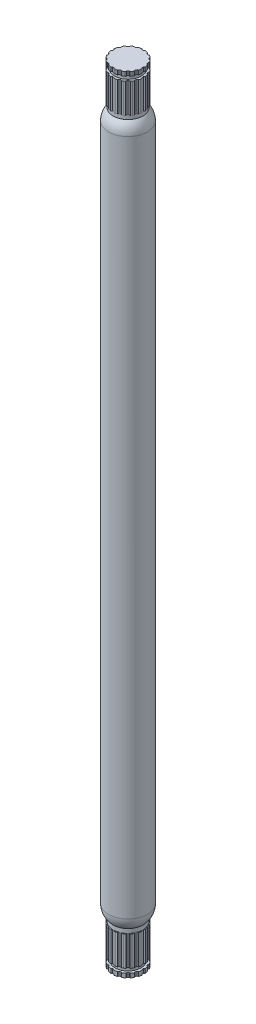
SolidWorks part; units mm, degrees
ref_plane "Front Plane" through (0, 0, 0) normal (0, 0, 1) x (1, 0, 0)
ref_plane "Top Plane" through (0, 0, 0) normal (0, 1, 0) x (1, 0, 0)
ref_plane "Right Plane" through (0, 0, 0) normal (1, 0, 0) x (0, 0, -1)
sketch "Sketch1" plane through (0, 0, 0) normal (0, 1, 0) x (1, 0, 0)
  circle A0 centre (0, 0) radius 11.65
  dimension "D1" = 23.3
extrude "Boss-Extrude1" add sketch "Sketch1" along normal blind 420
sketch "Sketch3" plane through (0, 420, 0) normal (0, 1, 0) x (1, 0, 0)
  circle A0 centre (0, 0) radius 8.9
  dimension "D1" = 17.8
extrude "Boss-Extrude2" add sketch "Sketch3" along normal blind 2.5
sketch "Sketch4" plane through (0, 422.5, 0) normal (0, 1, 0) x (1, 0, 0)
  line L0 (0, 12.8994) -> (0, 9.45) construction
  line L1 (-0.45, 8.8886) -> (0.45, 8.8886)
  line L2 (8.0398, -3.8173) -> (8.3842, -2.9858)
  line L3 (0.45, 8.8886) -> (0.9864, 9.3984)
  line L4 (-0.45, 8.8886) -> (-0.9864, 9.3984)
  line L5 (-0.9864, 9.3984) -> (-2.7571, 9.0388)
  line L6 (0.9864, 9.3984) -> (2.7571, 9.0388)
  line L7 (2.9858, 8.3842) -> (3.8173, 8.0398)
  line L8 (5.967, 6.6034) -> (6.6034, 5.967)
  line L9 (3.8173, 8.0398) -> (4.5079, 8.3055)
  line L10 (4.5079, 8.3055) -> (6.0063, 7.2957)
  line L11 (2.9858, 8.3842) -> (2.6853, 9.0605)
  line L12 (2.6853, 9.0605) -> (0.9118, 9.4059)
  line L15 (6.6034, 5.967) -> (7.3432, 5.9482)
  line L16 (7.3432, 5.9482) -> (8.341, 4.4419)
  line L17 (5.967, 6.6034) -> (5.9482, 7.3432)
  line L18 (5.9482, 7.3432) -> (4.4419, 8.341)
  line L19 (8.8886, -0.45) -> (8.8886, 0.45)
  line L20 (8.3842, 2.9858) -> (8.0398, 3.8173)
  line L21 (8.3842, 2.9858) -> (9.0605, 2.6853)
  line L22 (9.0605, 2.6853) -> (9.4059, 0.9118)
  line L23 (8.0398, 3.8173) -> (8.3055, 4.5079)
  line L24 (8.3055, 4.5079) -> (7.2957, 6.0063)
  line L27 (8.8886, -0.45) -> (9.3984, -0.9864)
  line L28 (9.3984, -0.9864) -> (9.0388, -2.7571)
  line L29 (8.8886, 0.45) -> (9.3984, 0.9864)
  line L30 (9.3984, 0.9864) -> (9.0388, 2.7571)
  line L33 (8.0398, -3.8173) -> (8.3055, -4.5079)
  line L34 (8.3055, -4.5079) -> (7.2957, -6.0063)
  line L35 (8.3842, -2.9858) -> (9.0605, -2.6853)
  line L36 (9.0605, -2.6853) -> (9.4059, -0.9118)
  line L37 (2.9858, -8.3842) -> (3.8173, -8.0398)
  line L38 (5.967, -6.6034) -> (6.6034, -5.967)
  line L39 (5.967, -6.6034) -> (5.9482, -7.3432)
  line L40 (5.9482, -7.3432) -> (4.4419, -8.341)
  line L41 (6.6034, -5.967) -> (7.3432, -5.9482)
  line L42 (7.3432, -5.9482) -> (8.341, -4.4419)
  line L45 (2.9858, -8.3842) -> (2.6853, -9.0605)
  line L46 (2.6853, -9.0605) -> (0.9118, -9.4059)
  line L47 (3.8173, -8.0398) -> (4.5079, -8.3055)
  line L48 (4.5079, -8.3055) -> (6.0063, -7.2957)
  line L49 (-2.9858, -8.3842) -> (-3.8173, -8.0398)
  line L50 (-0.45, -8.8886) -> (0.45, -8.8886)
  line L51 (-0.45, -8.8886) -> (-0.9864, -9.3984)
  line L52 (-0.9864, -9.3984) -> (-2.7571, -9.0388)
  line L53 (0.45, -8.8886) -> (0.9864, -9.3984)
  line L54 (0.9864, -9.3984) -> (2.7571, -9.0388)
  line L57 (-3.8173, -8.0398) -> (-4.5079, -8.3055)
  line L58 (-4.5079, -8.3055) -> (-6.0063, -7.2957)
  line L59 (-2.9858, -8.3842) -> (-2.6853, -9.0605)
  line L60 (-2.6853, -9.0605) -> (-0.9118, -9.4059)
  line L61 (-8.0398, -3.8173) -> (-8.3842, -2.9858)
  line L62 (-5.967, -6.6034) -> (-6.6034, -5.967)
  line L63 (-6.6034, -5.967) -> (-7.3432, -5.9482)
  line L64 (-7.3432, -5.9482) -> (-8.341, -4.4419)
  line L65 (-5.967, -6.6034) -> (-5.9482, -7.3432)
  line L66 (-5.9482, -7.3432) -> (-4.4419, -8.341)
  line L67 (0, -8.8886) -> (0, -8.9) construction
  line L68 (0, -9.45) -> (0, -14.34) construction
  line L69 (-8.3842, -2.9858) -> (-9.0605, -2.6853)
  line L70 (-9.0605, -2.6853) -> (-9.4059, -0.9118)
  line L71 (-8.0398, -3.8173) -> (-8.3055, -4.5079)
  line L72 (-8.3055, -4.5079) -> (-7.2957, -6.0063)
  line L73 (-8.8886, -0.45) -> (-8.8886, 0.45)
  line L75 (-8.8886, 0.45) -> (-9.3984, 0.9864)
  line L76 (-9.3984, 0.9864) -> (-9.0388, 2.7571)
  line L77 (-8.8886, -0.45) -> (-9.3984, -0.9864)
  line L78 (-9.3984, -0.9864) -> (-9.0388, -2.7571)
  line L79 (-8.3842, 2.9858) -> (-8.0398, 3.8173)
  line L81 (-8.0398, 3.8173) -> (-8.3055, 4.5079)
  line L82 (-8.3055, 4.5079) -> (-7.2957, 6.0063)
  line L83 (-8.3842, 2.9858) -> (-9.0605, 2.6853)
  line L84 (-9.0605, 2.6853) -> (-9.4059, 0.9118)
  line L85 (-3.8173, 8.0398) -> (-2.9858, 8.3842)
  line L86 (-6.6034, 5.967) -> (-5.967, 6.6034)
  line L87 (-5.967, 6.6034) -> (-5.9482, 7.3432)
  line L88 (-5.9482, 7.3432) -> (-4.4419, 8.341)
  line L89 (-6.6034, 5.967) -> (-7.3432, 5.9482)
  line L90 (-7.3432, 5.9482) -> (-8.341, 4.4419)
  line L93 (-2.9858, 8.3842) -> (-2.6853, 9.0605)
  line L94 (-2.6853, 9.0605) -> (-0.9118, 9.4059)
  line L95 (-3.8173, 8.0398) -> (-4.5079, 8.3055)
  line L96 (-4.5079, 8.3055) -> (-6.0063, 7.2957)
  circle A0 centre (0, 0) radius 9.45
  arc A1 (2.9858, 8.3842) -> (0.45, 8.8886) centre (0, 0) ccw
  arc A3 (8.3842, -2.9858) -> (8.8886, -0.45) centre (0, 0) ccw
  arc A4 (8.8886, 0.45) -> (8.3842, 2.9858) centre (0, 0) ccw
  arc A9 (-0.45, 8.8886) -> (-2.9858, 8.3842) centre (0, 0) ccw
  arc A10 (-3.8173, 8.0398) -> (-5.967, 6.6034) centre (0, 0) ccw
  arc A11 (-6.6034, 5.967) -> (-8.0398, 3.8173) centre (0, 0) ccw
  arc A12 (-8.3842, 2.9858) -> (-8.8886, 0.45) centre (0, 0) ccw
  arc A13 (-8.8886, -0.45) -> (-8.3842, -2.9858) centre (0, 0) ccw
  point P120 (0, 0)
  point P126 (0, 0)
  circle M1 centre (0, 0) radius 8.9
  dimension "D1" = 17.8
  dimension "D2" = 18.9
  dimension "D5" = 0.74
  dimension "D6" = 0.74
  dimension "D7" = 16
extrude "Boss-Extrude6" add sketch "Sketch4" along normal blind 17.8 contours L86 L79 L73 L61 L62 L49 L50 L37 L38 L2 L19 L20 L8 L7 L1 L85 M1 | L94 L5 L93 L4 M1 | L88 L96 L87 L95 M1 | L82 L90 L81 L89 M1 | L76 L84 L75 L83 M1 | L10 L18 L9 L17 M1 | L6 L12 L3 L11 M1 | L16 L24 L15 L23 M1 | L22 L30 L21 L29 M1 | L28 L36 L27 L35 M1 | L34 L42 L33 L41 M1 | L40 L48 L39 L47 M1 | L46 L54 L45 L53 M1 | L52 L60 L51 L59 M1 | L58 L66 L57 L65 M1 | L64 L72 L63 L71 M1 | L70 L78 L69 L77 M1 region at (-1.7793, 422.5, -8.9454) region at (0, 422.5, 0) region at (1.7793, 422.5, -8.9454) region at (-5.0671, 422.5, -7.5835) region at (5.0671, 422.5, -7.5835) region at (-7.5835, 422.5, -5.0671) region at (7.5835, 422.5, -5.0671) region at (-8.9454, 422.5, -1.7793) region at (8.9454, 422.5, -1.7793) region at (-8.9454, 422.5, 1.7793) region at (8.9454, 422.5, 1.7793) region at (-7.5835, 422.5, 5.0671) region at (7.5835, 422.5, 5.0671) region at (-5.0671, 422.5, 7.5835) region at (5.0671, 422.5, 7.5835) region at (-1.7793, 422.5, 8.9454) region at (1.7793, 422.5, 8.9454)
sketch "Sketch8" plane through (0, 440.3, 0) normal (0, 1, 0) x (1, 0, 0)
  circle A0 centre (0, 0) radius 8.0167
extrude "Boss-Extrude7" add sketch "Sketch8" along normal blind 2.5
sketch "Sketch9" plane through (0, 442.8, 0) normal (0, 1, 0) x (1, 0, 0)
  line L0 (0, 12.7838) -> (0, 9.4068) construction
  line L1 (-0.45, 8.8886) -> (0.45, 8.8886)
  line L2 (0.45, 8.8886) -> (0.9803, 9.3926)
  line L3 (0.9803, 9.3926) -> (2.6887, 9.0527)
  line L4 (-0.45, 8.8886) -> (-0.9803, 9.3926)
  line L5 (-0.9803, 9.3926) -> (-2.6887, 9.0527)
  line L6 (9.3926, 0.9803) -> (9.0527, 2.6887)
  line L7 (8.8886, 0.45) -> (8.8886, -0.45)
  line L8 (8.8886, -0.45) -> (9.3926, -0.9803)
  line L9 (8.8886, 0.45) -> (9.3926, 0.9803)
  line L10 (9.3926, -0.9803) -> (9.0527, -2.6887)
  line L11 (0.9803, -9.3926) -> (2.6887, -9.0527)
  line L12 (0.45, -8.8886) -> (-0.45, -8.8886)
  line L13 (-0.45, -8.8886) -> (-0.9803, -9.3926)
  line L14 (0.45, -8.8886) -> (0.9803, -9.3926)
  line L15 (-0.9803, -9.3926) -> (-2.6887, -9.0527)
  line L16 (-9.3926, -0.9803) -> (-9.0527, -2.6887)
  line L17 (-8.8886, -0.45) -> (-8.8886, 0.45)
  line L18 (-8.8886, 0.45) -> (-9.3926, 0.9803)
  line L19 (-8.8886, -0.45) -> (-9.3926, -0.9803)
  line L20 (-9.3926, 0.9803) -> (-9.0527, 2.6887)
  line L21 (2.6887, 9.0527) -> (0.9803, 9.3926)
  line L22 (2.9858, 8.3842) -> (3.8173, 8.0398)
  line L23 (3.8173, 8.0398) -> (4.5001, 8.3025)
  line L24 (2.9858, 8.3842) -> (2.6887, 9.0527)
  line L25 (4.5001, 8.3025) -> (5.9484, 7.3347)
  line L26 (5.9484, 7.3347) -> (4.5001, 8.3025)
  line L27 (5.967, 6.6034) -> (6.6034, 5.967)
  line L28 (6.6034, 5.967) -> (7.3347, 5.9484)
  line L29 (5.967, 6.6034) -> (5.9484, 7.3347)
  line L30 (7.3347, 5.9484) -> (8.3025, 4.5001)
  line L31 (8.3025, 4.5001) -> (7.3347, 5.9484)
  line L32 (8.0398, 3.8173) -> (8.3842, 2.9858)
  line L33 (8.3842, 2.9858) -> (9.0527, 2.6887)
  line L34 (8.0398, 3.8173) -> (8.3025, 4.5001)
  line L35 (9.0527, 2.6887) -> (9.3926, 0.9803)
  line L36 (9.3926, 0.9803) -> (9.0527, 2.6887)
  line L37 (8.8886, 0.45) -> (8.8886, -0.45)
  line L38 (8.8886, -0.45) -> (9.3926, -0.9803)
  line L39 (8.8886, 0.45) -> (9.3926, 0.9803)
  line L40 (9.3926, -0.9803) -> (9.0527, -2.6887)
  line L41 (9.0527, -2.6887) -> (9.3926, -0.9803)
  line L42 (8.3842, -2.9858) -> (8.0398, -3.8173)
  line L43 (8.0398, -3.8173) -> (8.3025, -4.5001)
  line L44 (8.3842, -2.9858) -> (9.0527, -2.6887)
  line L45 (8.3025, -4.5001) -> (7.3347, -5.9484)
  line L46 (7.3347, -5.9484) -> (8.3025, -4.5001)
  line L47 (6.6034, -5.967) -> (5.967, -6.6034)
  line L48 (5.967, -6.6034) -> (5.9484, -7.3347)
  line L49 (6.6034, -5.967) -> (7.3347, -5.9484)
  line L50 (5.9484, -7.3347) -> (4.5001, -8.3025)
  line L51 (4.5001, -8.3025) -> (5.9484, -7.3347)
  line L52 (3.8173, -8.0398) -> (2.9858, -8.3842)
  line L53 (2.9858, -8.3842) -> (2.6887, -9.0527)
  line L54 (3.8173, -8.0398) -> (4.5001, -8.3025)
  line L55 (2.6887, -9.0527) -> (0.9803, -9.3926)
  line L56 (0.9803, -9.3926) -> (2.6887, -9.0527)
  line L57 (0.45, -8.8886) -> (-0.45, -8.8886)
  line L58 (-0.45, -8.8886) -> (-0.9803, -9.3926)
  line L59 (0.45, -8.8886) -> (0.9803, -9.3926)
  line L60 (-0.9803, -9.3926) -> (-2.6887, -9.0527)
  line L61 (-2.6887, -9.0527) -> (-0.9803, -9.3926)
  line L62 (-2.9858, -8.3842) -> (-3.8173, -8.0398)
  line L63 (-3.8173, -8.0398) -> (-4.5001, -8.3025)
  line L64 (-2.9858, -8.3842) -> (-2.6887, -9.0527)
  line L65 (-4.5001, -8.3025) -> (-5.9484, -7.3347)
  line L66 (-5.9484, -7.3347) -> (-4.5001, -8.3025)
  line L67 (-5.967, -6.6034) -> (-6.6034, -5.967)
  line L68 (-6.6034, -5.967) -> (-7.3347, -5.9484)
  line L69 (-5.967, -6.6034) -> (-5.9484, -7.3347)
  line L70 (-7.3347, -5.9484) -> (-8.3025, -4.5001)
  line L71 (-8.3025, -4.5001) -> (-7.3347, -5.9484)
  line L72 (-8.0398, -3.8173) -> (-8.3842, -2.9858)
  line L73 (-8.3842, -2.9858) -> (-9.0527, -2.6887)
  line L74 (-8.0398, -3.8173) -> (-8.3025, -4.5001)
  line L75 (-9.0527, -2.6887) -> (-9.3926, -0.9803)
  line L76 (-9.3926, -0.9803) -> (-9.0527, -2.6887)
  line L77 (-8.8886, -0.45) -> (-8.8886, 0.45)
  line L78 (-8.8886, 0.45) -> (-9.3926, 0.9803)
  line L79 (-8.8886, -0.45) -> (-9.3926, -0.9803)
  line L80 (-9.3926, 0.9803) -> (-9.0527, 2.6887)
  line L81 (-9.0527, 2.6887) -> (-9.3926, 0.9803)
  line L82 (-8.3842, 2.9858) -> (-8.0398, 3.8173)
  line L83 (-8.0398, 3.8173) -> (-8.3025, 4.5001)
  line L84 (-8.3842, 2.9858) -> (-9.0527, 2.6887)
  line L85 (-8.3025, 4.5001) -> (-7.3347, 5.9484)
  line L86 (-7.3347, 5.9484) -> (-8.3025, 4.5001)
  line L87 (-6.6034, 5.967) -> (-5.967, 6.6034)
  line L88 (-5.967, 6.6034) -> (-5.9484, 7.3347)
  line L89 (-6.6034, 5.967) -> (-7.3347, 5.9484)
  line L90 (-5.9484, 7.3347) -> (-4.5001, 8.3025)
  line L91 (-4.5001, 8.3025) -> (-5.9484, 7.3347)
  line L92 (-3.8173, 8.0398) -> (-2.9858, 8.3842)
  line L93 (-2.9858, 8.3842) -> (-2.6887, 9.0527)
  line L94 (-3.8173, 8.0398) -> (-4.5001, 8.3025)
  line L95 (-2.6887, 9.0527) -> (-0.9803, 9.3926)
  line L96 (0, 8.9) -> (0, -1.5385) construction
  arc A0 (2.7084, 9.0085) -> (0.9452, 9.3592) centre (0, 0) ccw
  arc A1 (-5.967, 6.6034) -> (-3.8173, 8.0398) centre (0, 0) ccw
  arc A2 (-0.9452, 9.3592) -> (-2.7084, 9.0085) centre (0, 0) ccw
  arc A3 (-4.4548, 8.2851) -> (-5.9496, 7.2863) centre (0, 0) ccw
  arc A4 (-7.2863, 5.9496) -> (-8.2851, 4.4548) centre (0, 0) ccw
  arc A5 (-9.0085, 2.7084) -> (-9.3592, 0.9452) centre (0, 0) ccw
  arc A6 (-9.3592, -0.9452) -> (-9.0085, -2.7084) centre (0, 0) ccw
  arc A7 (-8.2851, -4.4548) -> (-7.2863, -5.9496) centre (0, 0) ccw
  arc A8 (5.9496, 7.2863) -> (4.4548, 8.2851) centre (0, 0) ccw
  arc A9 (8.2851, 4.4548) -> (7.2863, 5.9496) centre (0, 0) ccw
  arc A10 (9.3592, 0.9452) -> (9.0085, 2.7084) centre (0, 0) ccw
  arc A11 (9.0085, -2.7084) -> (9.3592, -0.9452) centre (0, 0) ccw
  arc A12 (7.2863, -5.9496) -> (8.2851, -4.4548) centre (0, 0) ccw
  arc A13 (4.4548, -8.2851) -> (5.9496, -7.2863) centre (0, 0) ccw
  arc A14 (0.9452, -9.3592) -> (2.7084, -9.0085) centre (0, 0) ccw
  arc A15 (-2.7084, -9.0085) -> (-0.9452, -9.3592) centre (0, 0) ccw
  arc A16 (-5.9496, -7.2863) -> (-4.4548, -8.2851) centre (0, 0) ccw
  point P41 (0, 0)
  point P131 (0, 0)
  circle M2 centre (0, 0) radius 8.0167
  dimension "D1" = 4
  dimension "D2" = 16
extrude "Boss-Extrude9" add sketch "Sketch9" along normal blind 2.5 contours M2 | L94 A3 L91 L88 L87 A1 L82 L17 L72 L67 L62 L12 L52 L47 L42 L7 L32 L27 L22 L1 L92 M2 | L89 A4 L86 L83 A1 | L84 A5 L81 L18 A1 | L19 A6 L76 L73 A1 | L74 A7 L71 L68 A1 | L69 A16 L66 L63 A1 | L64 A15 L61 L13 A1 | L14 A14 L56 L53 A1 | L54 A13 L51 L48 A1 | L49 A12 L46 L43 A1 | L44 A11 L41 L8 A1 | L9 A10 L36 L33 A1 | L34 A9 L31 L28 A1 | L29 A8 L26 L23 A1 | L4 A2 L95 L93 A1 | A1 L24 A0 L21 L2 region at (-1.7783, 442.8, -8.9399) region at (0, 442.8, -8.6372) region at (1.7783, 442.8, -8.9399) region at (5.0641, 442.8, -7.5789) region at (7.5789, 442.8, -5.0641) region at (8.9399, 442.8, -1.7783) region at (-7.5789, 442.8, -5.0641) region at (8.9399, 442.8, 1.7783) region at (-8.9399, 442.8, -1.7783) region at (7.5789, 442.8, 5.0641) region at (-8.9399, 442.8, 1.7783) region at (5.0641, 442.8, 7.5789) region at (-7.5789, 442.8, 5.0641) region at (1.7783, 442.8, 8.9399) region at (-5.0641, 442.8, 7.5789) region at (-1.7783, 442.8, 8.9399) region at (0, 442.8, 0)
fillet "Fillet1" radius 10 1 edges at (0, 420, 11.65)
sketch "Sketch13" plane through (0, 0, 0) normal (0, -1, 0) x (1, 0, 0)
  circle A0 centre (0, 0) radius 8.8974
extrude "Boss-Extrude10" add sketch "Sketch13" along normal blind 2.5
sketch "Sketch14" plane through (0, -2.5, 0) normal (0, -1, 0) x (1, 0, 0)
  line L0 (0, 13.861) -> (0, 9.4485) construction
  line L1 (-0.4084, 8.8858) -> (-0.4557, 8.8858)
  line L2 (0.4084, 8.8858) -> (0.4382, 8.8858)
  line L3 (0.4382, 8.8858) -> (0.9644, 9.412)
  line L4 (-0.4557, 8.8858) -> (-0.9819, 9.412)
  line L5 (-0.9819, 9.412) -> (-2.7528, 9.0329)
  line L6 (0.9644, 9.412) -> (2.7354, 9.0329)
  line L7 (4.4928, 8.3265) -> (5.9839, 7.2985)
  line L8 (2.9794, 8.3838) -> (2.6947, 9.0713)
  line L9 (3.8053, 8.0417) -> (4.4928, 8.3265)
  line L10 (2.6947, 9.0713) -> (0.9135, 9.3988)
  line L11 (7.3372, 5.9733) -> (8.3214, 4.453)
  line L12 (5.961, 6.6055) -> (5.961, 7.3496)
  line L13 (6.5931, 5.9733) -> (7.3372, 5.9733)
  line L14 (5.961, 7.3496) -> (4.4407, 8.3338)
  line L15 (9.0646, 2.7108) -> (9.3921, 0.9296)
  line L16 (8.035, 3.8215) -> (8.3198, 4.509)
  line L17 (8.3771, 2.9956) -> (9.0646, 2.7108)
  line L18 (8.3198, 4.509) -> (7.2919, 6)
  line L19 (9.412, -0.9644) -> (9.0329, -2.7354)
  line L20 (8.8858, 0.4557) -> (9.412, 0.9819)
  line L21 (8.8858, -0.4382) -> (9.412, -0.9644)
  line L22 (9.412, 0.9819) -> (9.0329, 2.7528)
  line L23 (8.3265, -4.4928) -> (7.2985, -5.9839)
  line L24 (8.3838, -2.9794) -> (9.0713, -2.6947)
  line L25 (8.0417, -3.8053) -> (8.3265, -4.4928)
  line L26 (9.0713, -2.6947) -> (9.3988, -0.9135)
  line L27 (5.9733, -7.3372) -> (4.453, -8.3214)
  line L28 (6.6055, -5.961) -> (7.3496, -5.961)
  line L29 (5.9733, -6.5931) -> (5.9733, -7.3372)
  line L30 (7.3496, -5.961) -> (8.3338, -4.4407)
  line L31 (2.7108, -9.0646) -> (0.9296, -9.3921)
  line L32 (3.8215, -8.035) -> (4.509, -8.3198)
  line L33 (2.9956, -8.3771) -> (2.7108, -9.0646)
  line L34 (4.509, -8.3198) -> (6, -7.2919)
  line L35 (-0.9644, -9.412) -> (-2.7354, -9.0329)
  line L36 (0.4557, -8.8858) -> (0.9819, -9.412)
  line L37 (-0.4382, -8.8858) -> (-0.9644, -9.412)
  line L38 (0.9819, -9.412) -> (2.7528, -9.0329)
  line L39 (-4.4928, -8.3265) -> (-5.9839, -7.2985)
  line L40 (-2.9794, -8.3838) -> (-2.6947, -9.0713)
  line L41 (-3.8053, -8.0417) -> (-4.4928, -8.3265)
  line L42 (-2.6947, -9.0713) -> (-0.9135, -9.3988)
  line L43 (-7.3372, -5.9733) -> (-8.3214, -4.453)
  line L44 (-5.961, -6.6055) -> (-5.961, -7.3496)
  line L45 (-6.5931, -5.9733) -> (-7.3372, -5.9733)
  line L46 (-5.961, -7.3496) -> (-4.4407, -8.3338)
  line L47 (-9.0646, -2.7108) -> (-9.3921, -0.9296)
  line L48 (-8.035, -3.8215) -> (-8.3198, -4.509)
  line L49 (-8.3771, -2.9956) -> (-9.0646, -2.7108)
  line L50 (-8.3198, -4.509) -> (-7.2919, -6)
  line L51 (-9.412, 0.9644) -> (-9.0329, 2.7354)
  line L52 (-8.8858, -0.4557) -> (-9.412, -0.9819)
  line L53 (-8.8858, 0.4382) -> (-9.412, 0.9644)
  line L54 (-9.412, -0.9819) -> (-9.0329, -2.7528)
  line L55 (-8.3265, 4.4928) -> (-7.2985, 5.9839)
  line L56 (-8.3838, 2.9794) -> (-9.0713, 2.6947)
  line L57 (-8.0417, 3.8053) -> (-8.3265, 4.4928)
  line L58 (-9.0713, 2.6947) -> (-9.3988, 0.9135)
  line L59 (-5.9733, 7.3372) -> (-4.453, 8.3214)
  line L60 (-6.6055, 5.961) -> (-7.3496, 5.961)
  line L61 (-5.9733, 6.5931) -> (-5.9733, 7.3372)
  line L62 (-7.3496, 5.961) -> (-8.3338, 4.4407)
  line L63 (-2.7108, 9.0646) -> (-0.9296, 9.3921)
  line L64 (-3.8215, 8.035) -> (-4.509, 8.3198)
  line L65 (-2.9956, 8.3771) -> (-2.7108, 9.0646)
  line L66 (-4.509, 8.3198) -> (-6, 7.2919)
  line L67 (0, -8.8952) -> (0, -17.3327) construction
  line L68 (-0.4557, 8.8858) -> (0.4382, 8.8858)
  line L69 (2.9794, 8.3838) -> (3.8053, 8.0417)
  line L70 (5.961, 6.6055) -> (6.5931, 5.9733)
  line L71 (8.035, 3.8215) -> (8.3771, 2.9956)
  line L72 (8.8858, 0.4557) -> (8.8858, -0.4382)
  line L73 (8.3838, -2.9794) -> (8.0417, -3.8053)
  line L74 (6.6055, -5.961) -> (5.9733, -6.5931)
  line L75 (3.8215, -8.035) -> (2.9956, -8.3771)
  line L76 (0.4557, -8.8858) -> (-0.4382, -8.8858)
  line L77 (-2.9794, -8.3838) -> (-3.8053, -8.0417)
  line L78 (-5.961, -6.6055) -> (-6.5931, -5.9733)
  line L79 (-8.035, -3.8215) -> (-8.3771, -2.9956)
  line L80 (-8.8858, -0.4557) -> (-8.8858, 0.4382)
  line L81 (-8.3838, 2.9794) -> (-8.0417, 3.8053)
  line L82 (-6.6055, 5.961) -> (-5.9733, 6.5931)
  line L83 (-3.8215, 8.035) -> (-2.9956, 8.3771)
  circle A0 centre (0, 0) radius 9.4485
  arc A1 (-3.0231, 8.3657) -> (-3.7778, 8.0531) centre (0, 0) ccw
  arc A2 (-5.9944, 6.572) -> (-6.572, 5.9944) centre (0, 0) ccw
  arc A3 (3.7778, 8.0531) -> (3.0231, 8.3657) centre (0, 0) ccw
  arc A4 (6.572, 5.9944) -> (5.9944, 6.572) centre (0, 0) ccw
  arc A5 (8.3657, 3.0231) -> (8.0531, 3.7778) centre (0, 0) ccw
  arc A6 (-8.3657, -3.0231) -> (-8.0531, -3.7778) centre (0, 0) ccw
  arc A7 (-8.8858, 0.4084) -> (-8.8858, -0.4084) centre (0, 0) ccw
  arc A8 (-8.0531, 3.7778) -> (-8.3657, 3.0231) centre (0, 0) ccw
  arc A9 (5.9944, -6.572) -> (6.572, -5.9944) centre (0, 0) ccw
  arc A10 (8.0531, -3.7778) -> (8.3657, -3.0231) centre (0, 0) ccw
  arc A11 (8.8858, -0.4084) -> (8.8858, 0.4084) centre (0, 0) ccw
  arc A12 (3.0231, -8.3657) -> (3.7778, -8.0531) centre (0, 0) ccw
  arc A13 (-0.4084, -8.8858) -> (0.4084, -8.8858) centre (0, 0) ccw
  arc A14 (-3.7778, -8.0531) -> (-3.0231, -8.3657) centre (0, 0) ccw
  arc A15 (-6.572, -5.9944) -> (-5.9944, -6.572) centre (0, 0) ccw
  point P105 (0, 0)
  point P138 (0, 0)
  circle M2 centre (0, 0) radius 8.8974
  dimension "D1" = 16
  dimension "D2" = 16
extrude "Boss-Extrude11" add sketch "Sketch14" along normal blind 17.8 contours L83 L61 L82 L57 L81 L53 L80 L49 L79 L45 L78 L41 L77 L37 L76 L33 L75 L29 L74 L25 L73 M2 | L83 L64 L59 L66 L61 M2 | L65 L1 L4 L63 L5 M2 | L69 L8 L6 L10 L3 M2 | L70 L12 L7 L14 L9 M2 | L71 L16 L11 L18 L13 M2 | L72 L20 L15 L22 L17 M2 | L73 L24 L19 L26 L21 M2 | L74 L28 L23 L30 L25 M2 | L82 L60 L55 L62 L57 M2 | L81 L56 L51 L58 L53 M2 | L80 L52 L47 L54 L49 M2 | L77 L40 L35 L42 L37 M2 | L78 L44 L39 L46 L41 M2 | L79 L48 L43 L50 L45 M2 | L76 L36 L31 L38 L33 M2 | L75 L32 L27 L34 L29 M2 region at (0, -2.5, 0) region at (-1.7885, -2.5, 8.9415) region at (1.7694, -2.5, 8.9453) region at (-5.0741, -2.5, 7.5764) region at (5.058, -2.5, 7.5874) region at (-7.5872, -2.5, 5.0579) region at (7.5765, -2.5, 5.0741) region at (-8.9453, -2.5, 1.7694) region at (8.9415, -2.5, 1.7885) region at (-8.9415, -2.5, -1.7885) region at (8.9453, -2.5, -1.7694) region at (-7.5765, -2.5, -5.0741) region at (7.5872, -2.5, -5.058) region at (-5.058, -2.5, -7.5872) region at (5.0741, -2.5, -7.5764) region at (-1.7694, -2.5, -8.9453) region at (1.7885, -2.5, -8.9415)
sketch "Sketch15" plane through (0, -20.3, 0) normal (0, -1, 0) x (1, 0, 0)
  circle A0 centre (0, 0) radius 7.8049
extrude "Boss-Extrude12" add sketch "Sketch15" along normal blind 2.5
sketch "Sketch24" plane through (0, -22.8, 0) normal (0, -1, 0) x (1, 0, 0)
  line L0 (0, 10.4057) -> (0, -0.6204) construction
  line L1 (-0.4557, 8.8858) -> (0.4382, 8.8858)
  line L2 (0.4382, 8.8858) -> (0.9454, 9.3929)
  line L3 (-0.4557, 8.8858) -> (-0.957, 9.3871)
  line L4 (-0.957, 9.3871) -> (-2.7211, 9.0397)
  line L5 (0.9454, 9.3929) -> (2.7082, 9.0387)
  line L6 (4.4679, 8.3162) -> (5.961, 7.3143)
  line L7 (2.7082, 9.0387) -> (0.9454, 9.3929)
  line L8 (2.9794, 8.3838) -> (2.7082, 9.0387)
  line L9 (2.9794, 8.3838) -> (3.8053, 8.0417)
  line L10 (3.8053, 8.0417) -> (4.4679, 8.3162)
  line L11 (7.3103, 5.9733) -> (8.3063, 4.4764)
  line L12 (5.961, 7.3143) -> (4.4679, 8.3162)
  line L13 (5.961, 6.6055) -> (5.961, 7.3143)
  line L14 (5.961, 6.6055) -> (6.5931, 5.9733)
  line L15 (6.5931, 5.9733) -> (7.3103, 5.9733)
  line L16 (9.0397, 2.7211) -> (9.3871, 0.957)
  line L17 (8.3063, 4.4764) -> (7.3103, 5.9733)
  line L18 (8.035, 3.8215) -> (8.3063, 4.4764)
  line L19 (8.035, 3.8215) -> (8.3771, 2.9956)
  line L20 (8.3771, 2.9956) -> (9.0397, 2.7211)
  line L21 (9.3929, -0.9454) -> (9.0387, -2.7082)
  line L22 (9.3871, 0.957) -> (9.0397, 2.7211)
  line L23 (8.8858, 0.4557) -> (9.3871, 0.957)
  line L24 (8.8858, 0.4557) -> (8.8858, -0.4382)
  line L25 (8.8858, -0.4382) -> (9.3929, -0.9454)
  line L26 (8.3162, -4.4679) -> (7.3143, -5.961)
  line L27 (9.0387, -2.7082) -> (9.3929, -0.9454)
  line L28 (8.3838, -2.9794) -> (9.0387, -2.7082)
  line L29 (8.3838, -2.9794) -> (8.0417, -3.8053)
  line L30 (8.0417, -3.8053) -> (8.3162, -4.4679)
  line L31 (5.9733, -7.3103) -> (4.4764, -8.3063)
  line L32 (7.3143, -5.961) -> (8.3162, -4.4679)
  line L33 (6.6055, -5.961) -> (7.3143, -5.961)
  line L34 (6.6055, -5.961) -> (5.9733, -6.5931)
  line L35 (5.9733, -6.5931) -> (5.9733, -7.3103)
  line L36 (2.7211, -9.0397) -> (0.957, -9.3871)
  line L37 (4.4764, -8.3063) -> (5.9733, -7.3103)
  line L38 (3.8215, -8.035) -> (4.4764, -8.3063)
  line L39 (3.8215, -8.035) -> (2.9956, -8.3771)
  line L40 (2.9956, -8.3771) -> (2.7211, -9.0397)
  line L41 (-0.9454, -9.3929) -> (-2.7082, -9.0387)
  line L42 (0.957, -9.3871) -> (2.7211, -9.0397)
  line L43 (0.4557, -8.8858) -> (0.957, -9.3871)
  line L44 (0.4557, -8.8858) -> (-0.4382, -8.8858)
  line L45 (-0.4382, -8.8858) -> (-0.9454, -9.3929)
  line L46 (-4.4679, -8.3162) -> (-5.961, -7.3143)
  line L47 (-2.7082, -9.0387) -> (-0.9454, -9.3929)
  line L48 (-2.9794, -8.3838) -> (-2.7082, -9.0387)
  line L49 (-2.9794, -8.3838) -> (-3.8053, -8.0417)
  line L50 (-3.8053, -8.0417) -> (-4.4679, -8.3162)
  line L51 (-7.3103, -5.9733) -> (-8.3063, -4.4764)
  line L52 (-5.961, -7.3143) -> (-4.4679, -8.3162)
  line L53 (-5.961, -6.6055) -> (-5.961, -7.3143)
  line L54 (-5.961, -6.6055) -> (-6.5931, -5.9733)
  line L55 (-6.5931, -5.9733) -> (-7.3103, -5.9733)
  line L56 (-9.0397, -2.7211) -> (-9.3871, -0.957)
  line L57 (-8.3063, -4.4764) -> (-7.3103, -5.9733)
  line L58 (-8.035, -3.8215) -> (-8.3063, -4.4764)
  line L59 (-8.035, -3.8215) -> (-8.3771, -2.9956)
  line L60 (-8.3771, -2.9956) -> (-9.0397, -2.7211)
  line L61 (-9.3929, 0.9454) -> (-9.0387, 2.7082)
  line L62 (-9.3871, -0.957) -> (-9.0397, -2.7211)
  line L63 (-8.8858, -0.4557) -> (-9.3871, -0.957)
  line L64 (-8.8858, -0.4557) -> (-8.8858, 0.4382)
  line L65 (-8.8858, 0.4382) -> (-9.3929, 0.9454)
  line L66 (-8.3162, 4.4679) -> (-7.3143, 5.961)
  line L67 (-9.0387, 2.7082) -> (-9.3929, 0.9454)
  line L68 (-8.3838, 2.9794) -> (-9.0387, 2.7082)
  line L69 (-8.3838, 2.9794) -> (-8.0417, 3.8053)
  line L70 (-8.0417, 3.8053) -> (-8.3162, 4.4679)
  line L71 (-5.9733, 7.3103) -> (-4.4764, 8.3063)
  line L72 (-7.3143, 5.961) -> (-8.3162, 4.4679)
  line L73 (-6.6055, 5.961) -> (-7.3143, 5.961)
  line L74 (-6.6055, 5.961) -> (-5.9733, 6.5931)
  line L75 (-5.9733, 6.5931) -> (-5.9733, 7.3103)
  line L76 (-2.7211, 9.0397) -> (-0.957, 9.3871)
  line L77 (-4.4764, 8.3063) -> (-5.9733, 7.3103)
  line L78 (-3.8215, 8.035) -> (-4.4764, 8.3063)
  line L79 (-3.8215, 8.035) -> (-2.9956, 8.3771)
  line L80 (-2.9956, 8.3771) -> (-2.7211, 9.0397)
  circle A0 centre (0, 0) radius 8.8966
  circle A1 centre (0, 0) radius 9.4357
  point P18 (0, 0)
  point P21 (0, 0)
  point P112 (0, 0)
  circle M2 centre (0, 0) radius 7.8049
  dimension "D1" = 16
extrude "Boss-Extrude15" add sketch "Sketch24" along normal blind 2.5 contours M2 | L44 A0 L39 L34 L29 L24 L19 L14 L9 L1 L79 L74 L69 L64 L59 L54 L49 M2 | L37 A1 L35 A0 L39 L38 | L32 A1 L30 A0 L34 L33 | L27 A1 L25 A0 L29 L28 | L22 A1 L20 A0 L24 L23 | L17 A1 L15 A0 L19 L18 | L42 A1 L40 A0 L44 L43 | L47 A1 L45 A0 L49 L48 | L52 A1 L50 A0 L54 L53 | L57 A1 L55 A0 L59 L58 | L62 A1 L60 A0 L64 L63 | L67 A1 L65 A0 L69 L68 | L77 A1 L75 A0 L79 L78 | L72 A1 L70 A0 L74 L73 | L12 A1 L10 A0 L14 L13 | L7 A1 L2 A0 L9 L8 | L4 A1 L80 A0 L1 L3 region at (-1.7873, -22.8, 8.9383) region at (0, -22.8, 8.6345) region at (1.7693, -22.8, 8.9419) region at (-5.0718, -22.8, 7.5739) region at (5.0565, -22.8, 7.5842) region at (-7.5842, -22.8, 5.0565) region at (7.5739, -22.8, 5.0718) region at (-8.9419, -22.8, 1.7693) region at (8.9383, -22.8, 1.7873) region at (-8.9383, -22.8, -1.7873) region at (8.9419, -22.8, -1.7693) region at (-7.5739, -22.8, -5.0718) region at (7.5842, -22.8, -5.0565) region at (-5.0565, -22.8, -7.5842) region at (5.0718, -22.8, -7.5739) region at (-1.7693, -22.8, -8.9419) region at (1.7873, -22.8, -8.9383) region at (0, -22.8, 0)
fillet "Fillet2" radius 10 1 edges at (0, 0, 11.65)
